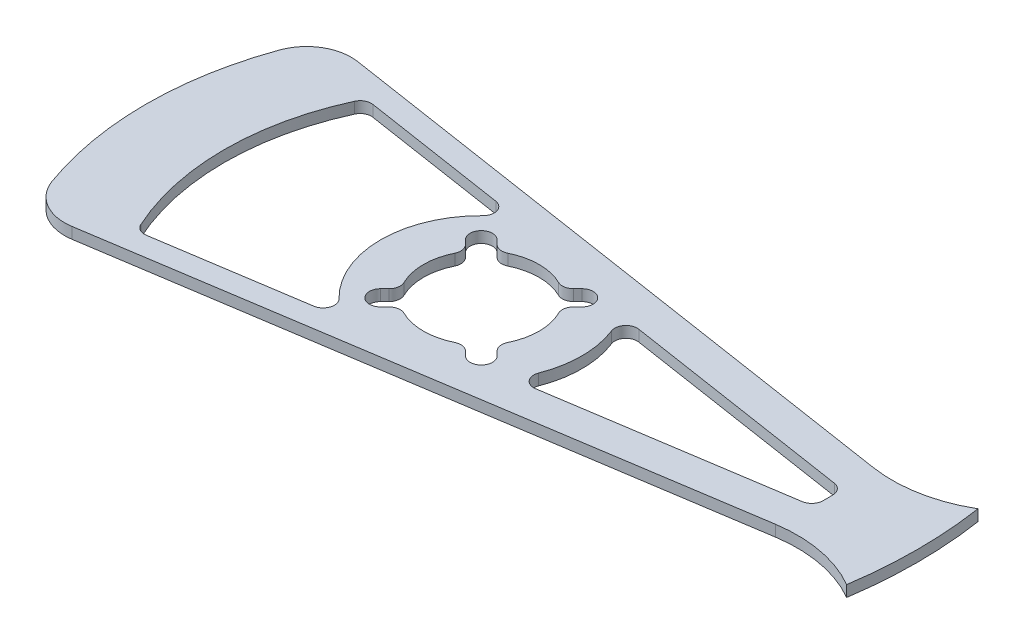
SolidWorks part; units mm, degrees
material "AISI 4340 Steel, normalized"
ref_plane "Front Plane" through (0, 0, 0) normal (0, 0, 1) x (1, 0, 0)
ref_plane "Top Plane" through (0, 0, 0) normal (0, 1, 0) x (1, 0, 0)
ref_plane "Right Plane" through (0, 0, 0) normal (1, 0, 0) x (0, 0, -1)
other "Center of Mass"
sketch "Sketch1" plane through (0, 0, 0) normal (0, 1, 0) x (1, 0, 0)
  line L0 (-170.9166, 84.1295) -> (194.8729, 27.8292)
  line L1 (-170.9166, -84.1295) -> (194.8729, -27.8292)
  line L2 (-130.6087, 65.076) -> (-28.7411, 49.3971)
  line L3 (-130.6087, -65.076) -> (-28.7411, -49.3971)
  line L4 (47.8972, 31.1766) -> (196.6759, 8.2773)
  line L5 (47.8972, -31.1766) -> (196.6759, -8.2773)
  line L6 (-33.0651, 24.0849) -> (-27.2657, 18.2854)
  line L7 (-28.575, -28.575) -> (28.575, -28.575) construction
  line L8 (-28.575, -28.575) -> (-28.575, 28.575) construction
  line L9 (-28.575, 28.575) -> (28.575, 28.575) construction
  line L10 (28.575, -28.575) -> (28.575, 28.575) construction
  line L11 (-28.575, -28.575) -> (28.575, 28.575) construction
  line L12 (-28.575, 28.575) -> (28.575, -28.575) construction
  line L13 (-24.0849, 33.0651) -> (-18.2854, 27.2657)
  line L14 (33.0651, 24.0849) -> (27.2657, 18.2854)
  line L15 (24.0849, 33.0651) -> (18.2854, 27.2657)
  line L16 (24.0849, -33.0651) -> (18.2854, -27.2657)
  line L17 (33.0651, -24.0849) -> (27.2657, -18.2854)
  line L18 (-33.0651, -24.0849) -> (-27.2657, -18.2854)
  line L19 (-24.0849, -33.0651) -> (-18.2854, -27.2657)
  line L20 (0, 0) -> (244.8246, 37.3019) construction
  circle A0 centre (0, 0) radius 57.15 construction
  circle A1 centre (0, 0) radius 247.65 construction
  arc A2 (244.8246, 37.3019) -> (244.8246, -37.3019) centre (0, 0) cw
  arc A3 (194.8729, -27.8292) -> (244.8246, -37.3019) centre (206.4647, -103.1423) cw
  arc A4 (194.8729, 27.8292) -> (244.8246, 37.3019) centre (206.4647, 103.1423) ccw
  circle A5 centre (0, 0) radius 190.5 construction
  arc A6 (-170.9166, 84.1295) -> (-170.9166, -84.1295) centre (0, 0) ccw
  circle A7 centre (0, 0) radius 196.85 construction
  circle A8 centre (0, 0) radius 145.923 construction
  arc A9 (-130.6087, 65.076) -> (-130.6087, -65.076) centre (0, 0) ccw
  arc A10 (-28.7411, 49.3971) -> (-28.7411, -49.3971) centre (0, 0) ccw
  arc A11 (47.8972, 31.1766) -> (47.8972, -31.1766) centre (0, 0) cw
  arc A12 (196.6759, 8.2773) -> (196.6759, -8.2773) centre (0, 0) cw
  circle A13 centre (0, 0) radius 32.8295
  circle A14 centre (-28.575, 28.575) radius 6.35
  circle A15 centre (28.575, 28.575) radius 6.35
  circle A16 centre (28.575, -28.575) radius 6.35
  circle A17 centre (-28.575, -28.575) radius 6.35
  point P18 (-190.5, 0)
  point P59 (0, 0)
  dimension "D1" = 495.3
  dimension "D2" = 50.8
  dimension "D3" = 17.5
  dimension "D4" = 114.3
  dimension "D5" = 57.15
  dimension "D6" = 76.2
  dimension "D9" = 44.577
  dimension "D12" = 65.659
  dimension "D14" = 12.7
  dimension "D15" = 4
  dimension "D7" = 12.7
  dimension "D8" = 12.7
  dimension "D10" = 19.05
  dimension "D11" = 19.05
  dimension "D13" = 57.15
extrude "Boss-Extrude1" add sketch "Sketch1" along normal blind 6.35 contours L0 A6 L1 A3 A2 A4 L2 A10 L3 A9 region at (11.2642, 0, -51.3405)
fillet "Fillet1" radius 6.35 8 edges at (47.8972, 3.175, 31.1766) (47.8972, 3.175, -31.1766) (196.6759, 3.175, -8.2773) (196.6759, 3.175, 8.2773) (-130.6087, 3.175, -65.076) (-130.6087, 3.175, 65.076) (-28.7411, 3.175, -49.3971) (-28.7411, 3.175, 49.3971)
fillet "Fillet2" radius 25.4 2 edges at (-170.9166, 3.175, -84.1295) (-170.9166, 3.175, 84.1295)
fillet "Fillet3" radius 6.35 8 edges at (-18.2854, 3.175, 27.2657) (18.2854, 3.175, 27.2657) (27.2657, 3.175, 18.2854) (27.2657, 3.175, -18.2854) (-18.2854, 3.175, -27.2657) (18.2854, 3.175, -27.2657) (-27.2657, 3.175, -18.2854) (-27.2657, 3.175, 18.2854)
